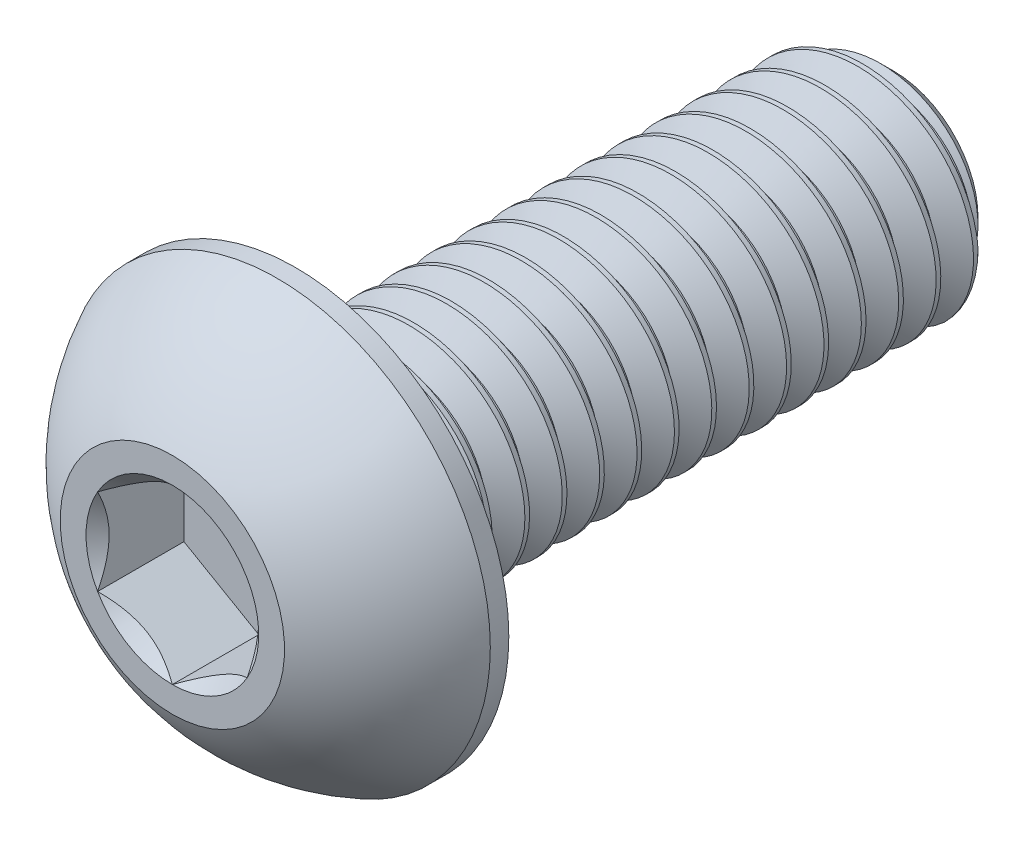
SolidWorks part; units mm, degrees
material "AISI 316 Annealed Stainless Steel Bar (SS)"
ref_plane "Front" through (0, 0, 0) normal (0, 0, 1) x (1, 0, 0)
ref_plane "Top" through (0, 0, 0) normal (0, 1, 0) x (1, 0, 0)
ref_plane "Right" through (0, 0, 0) normal (1, 0, 0) x (0, 0, -1)
sketch "Sketch1" plane through (0, 0, 0) normal (1, 0, 0) x (0, 0, -1)
  line L2 (1.65, 1.5) -> (9.65, 1.5)
  line L3 (9.65, 1.5) -> (9.65, 0)
  line L4 (9.65, 0) -> (1.65, 0)
  line L6 (1.4025, 2.85) -> (1.65, 2.85) construction
  line L7 (9.65, 1.5) -> (9.65, -1.5) construction
  line L8 (0, 0) -> (1.65, 0) construction
  line L9 (1.65, 2.85) -> (1.65, -2.85) construction
  line L11 (1.65, 1.5) -> (1.65, 0)
  line L13 (0, 1) -> (0, -1) construction
  line L14 (0, 1) -> (0, 1.5) construction
  arc A3 (0, 1.5) -> (1.4025, 2.85) centre (2.7948, 0) cw construction
  dimension "D1" = 0.2475
revolve "Revolve1" add sketch "Sketch1" angle 360 mid plane about L4
sketch "Sketch3" plane through (0, 0, -9.65) normal (0, 0, -1) x (-1, 0, 0)
  circle A0 centre (0, 0) radius 1.5
curve "Helix/Spiral1" pitch 0.5 height 8.5 radius 1.5 centre (0, 0, -9.65) axis (0, 0, 1) start towards (0, 1, 0)
sketch "Sketch2" plane through (0, 0, 0) normal (1, 0, 0) x (0, 0, -1)
  line L0 (9.65, 1.5) -> (10.0875, 1.5)
  line L1 (10.0875, 1.5) -> (9.9, 1.1752)
  line L2 (9.9, 1.1752) -> (9.8375, 1.1752)
  line L3 (9.8375, 1.1752) -> (9.65, 1.5)
  line L4 (9.7438, 1.3376) -> (9.9938, 1.3376) construction
  dimension "D1" = 60
  dimension "D2" = 0.0625
  dimension "D3" = 0.25
chamfer "Chamfer1" distance 0.375 angle 45 1 edges at (0, 1.5, -9.65)
sweep "Cut-Sweep1" cut profiles "Sketch2" path "Helix/Spiral1" align with end faces yes
sketch "Sketch7" plane through (0, 0, 0) normal (1, 0, 0) x (0, 0, -1)
  line L6 (1.4025, 2.85) -> (1.65, 2.85) construction
  line L8 (0, 0) -> (1.65, 0) construction
  line L11 (1.65, 2.85) -> (1.65, -2.85) construction
  line L12 (1.4025, 2.85) -> (1.65, 2.85)
  line L13 (0, 0) -> (1.65, 0)
  line L14 (0, 1) -> (0, -1) construction
  line L15 (1.65, 2.85) -> (1.65, 0)
  line L16 (0, 1.5) -> (0, 0)
  arc A2 (1.4025, 2.85) -> (0, 1.5) centre (2.7948, 0) ccw construction
  arc A3 (1.4025, 2.85) -> (0, 1.5) centre (2.7948, 0) ccw
revolve "Revolve2" add sketch "Sketch7" angle 360 mid plane about L13
sketch "Sketch5" plane through (0, 0, 0) normal (0, 0, 1) x (1, 0, 0)
  line L1 (1, -0.5774) -> (1, 0.5774)
  line L2 (1, 0.5774) -> (0, 1.1547)
  line L3 (0, 1.1547) -> (-1, 0.5774)
  line L4 (-1, 0.5774) -> (-1, -0.5774)
  line L5 (-1, -0.5774) -> (0, -1.1547)
  line L6 (0, -1.1547) -> (1, -0.5774)
  circle A0 centre (0, 0) radius 1 construction
extrude "Cut-Extrude2" cut sketch "Sketch5" against normal blind 1.155
sketch "Sketch6" plane through (0, 0, 0) normal (0, 0, 1) x (1, 0, 0)
  circle A0 centre (0, 0) radius 1.1547
extrude "Cut-Extrude3" cut sketch "Sketch6" against normal blind 1.155 draft 45
sketch "Sketch9" [suppressed] plane through (0, 0, -6.6) normal (0, 0, 1) x (1, 0, 0)
  circle A2 centre (0, 0) radius 6
extrude "Boss-Extrude2" [suppressed] add sketch "Sketch9" against normal offset from surface (19 mm away) 32 up to face at (0, 1.125, -9.65)
sketch "Sketch10" plane through (0, 0, 0) normal (1, 0, 0) x (0, 0, -1)
  line L0 (9.65, 1.5) -> (9.65, -1.5) construction
  point P0 (8.9, -1.5)
  dimension "D1" = 0.75
equation "\"D3@Helix/Spiral1\" = \"Lg@Sketch1\" + \"D4@Helix/Spiral1\""
equation "\"D2@Sketch2\" = \"D4@Helix/Spiral1\" * .125"
equation "\"D3@Sketch2\" = \"D4@Helix/Spiral1\" * .5"
equation "\"D1@Chamfer1\" = \"D4@Helix/Spiral1\" * .75"
equation "\"D1@Cut-Extrude2\" = \"Head Ht@Sketch1\" * .7"
equation "\"D1@Sketch1\" = \"Head Ht@Sketch1\" * .15"
equation "\"D1@Sketch10\" = \"D4@Helix/Spiral1\" * 1.5"
equation "\"D1@Cut-Extrude3\" = \"D1@Cut-Extrude2\""
